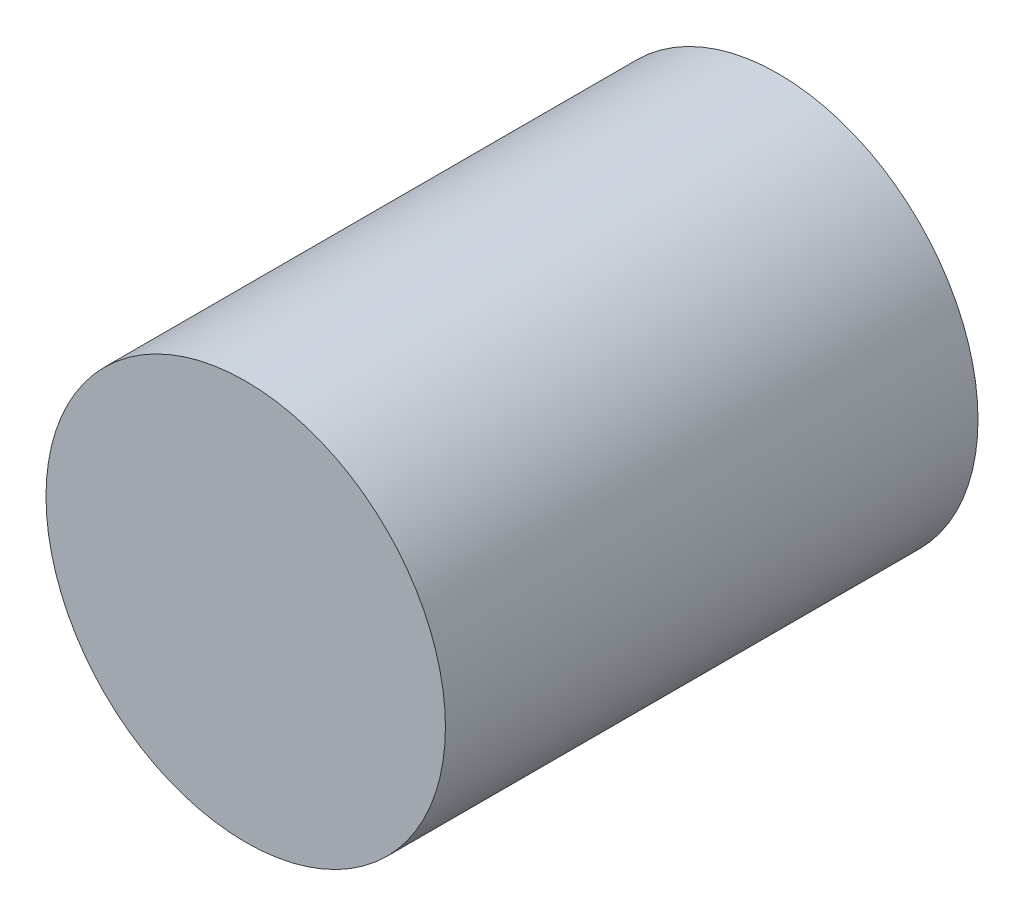
SolidWorks part; units mm, degrees
ref_plane "Front Plane" through (0, 0, 0) normal (0, 0, 1) x (1, 0, 0)
ref_plane "Top Plane" through (0, 0, 0) normal (0, 1, 0) x (1, 0, 0)
ref_plane "Right Plane" through (0, 0, 0) normal (1, 0, 0) x (0, 0, -1)
sketch "Sketch1" plane through (0, 0, 0) normal (0, 0, 1) x (1, 0, 0)
  circle A0 centre (0, 0) radius 15
  dimension "D1" = 30
extrude "Boss-Extrude1" add sketch "Sketch1" along normal blind 40
ref_axis "Axis1" through (0, 0, 40) along (0, 0, -1)
